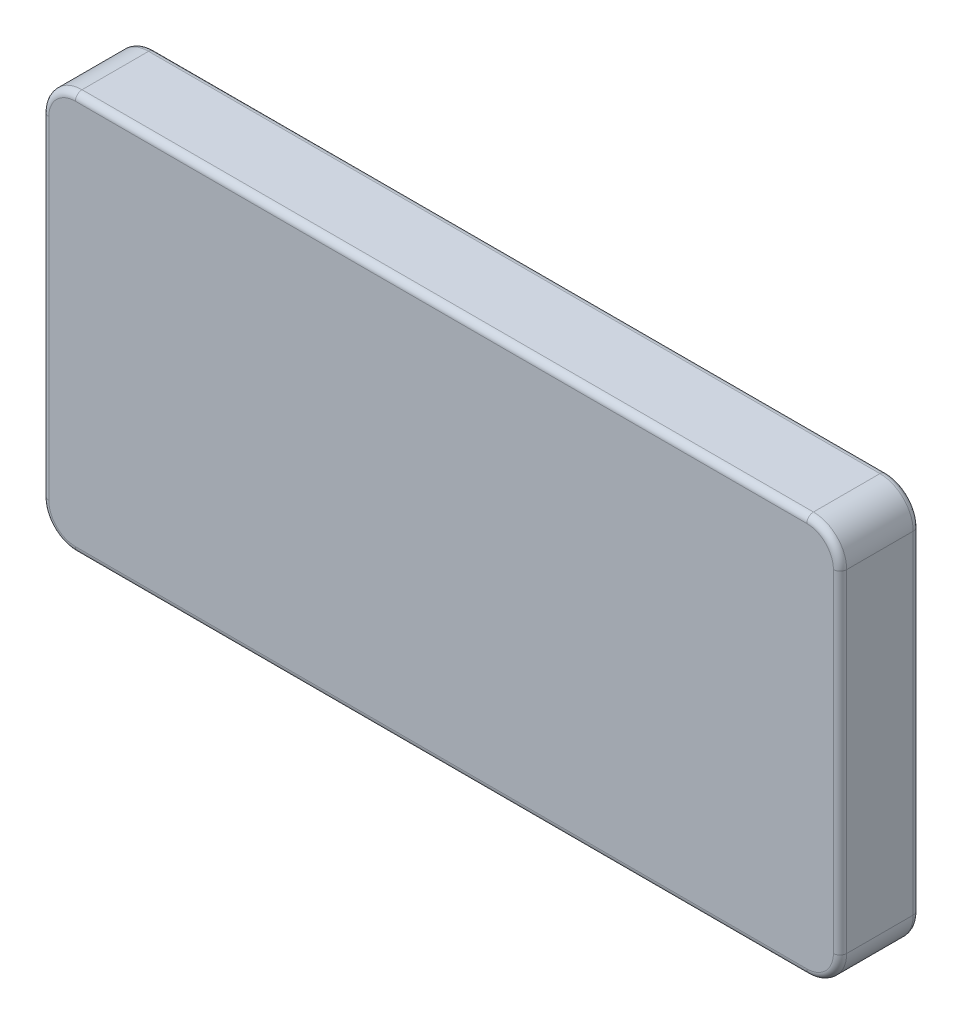
SolidWorks part; units mm, degrees
ref_plane "Front" through (0, 0, 0) normal (0, 0, 1) x (1, 0, 0)
ref_plane "Top" through (0, 0, 0) normal (0, 1, 0) x (1, 0, 0)
ref_plane "Right" through (0, 0, 0) normal (1, 0, 0) x (0, 0, -1)
sketch "Esquisse1" plane through (0, 0, 0) normal (0, 0, 1) x (1, 0, 0)
  line L1 (0, 0) -> (1200, 0)
  line L2 (0, 0) -> (0, 600)
  line L3 (0, 600) -> (1200, 600)
  line L4 (1200, 0) -> (1200, 600)
  dimension "D1" = 1200
  dimension "D2" = 600
extrude "Boss.-Extru.1" add sketch "Esquisse1" along normal blind 120
fillet "Congé1" radius 10 8 edges at (600, 0, 0) (1200, 300, 0) (600, 600, 0) (0, 300, 0) (600, 600, 120) (1200, 300, 120) (600, 0, 120) (0, 300, 120)
fillet "Congé2" radius 50 12 edges at (1197.0711, 2.9289, 2.9289) (1197.0711, 2.9289, 117.0711) (1197.0711, 597.0711, 2.9289) (1197.0711, 597.0711, 117.0711) (2.9289, 2.9289, 2.9289) (2.9289, 2.9289, 117.0711) (2.9289, 597.0711, 2.9289) (2.9289, 597.0711, 117.0711) (0, 600, 60) (0, 0, 60) (1200, 600, 60) (1200, 0, 60)
